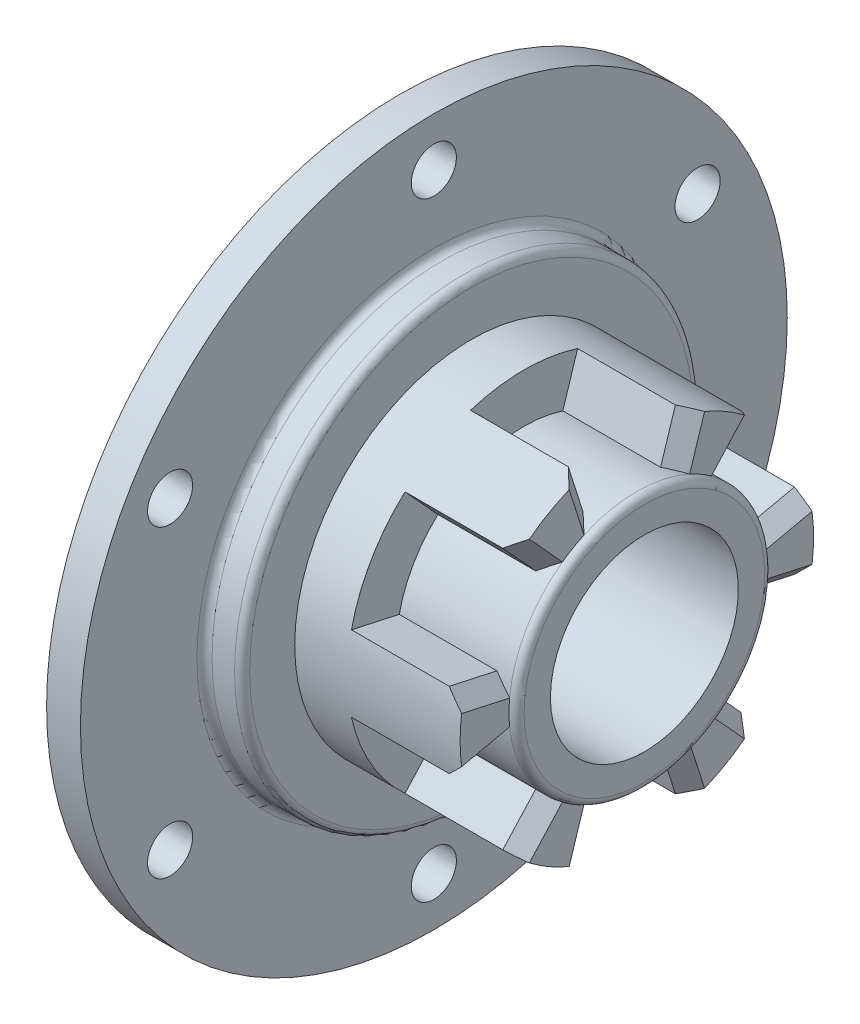
SolidWorks part; units mm, degrees
ref_plane "Front Plane" through (0, 0, 0) normal (0, 0, 1) x (1, 0, 0)
ref_plane "Top Plane" through (0, 0, 0) normal (0, 1, 0) x (1, 0, 0)
ref_plane "Right Plane" through (0, 0, 0) normal (1, 0, 0) x (0, 0, -1)
sketch "Sketch1" plane through (0, 0, 0) normal (0, 0, 1) x (1, 0, 0)
  line L0 (0, 31.5) -> (0, 34)
  line L1 (0, 34) -> (3.5, 34)
  line L2 (3.5, 34) -> (3.5, 47)
  line L3 (3.5, 47) -> (8, 47)
  line L4 (8, 47) -> (8, 30.5)
  line L5 (8, 30.5) -> (13, 30.5)
  line L6 (13, 30.5) -> (13, 23.5)
  line L7 (13, 23.5) -> (35, 23.5)
  line L8 (35, 23.5) -> (35, 17)
  line L9 (35, 17) -> (36, 17)
  line L10 (36, 17) -> (36, 12.5)
  line L11 (36, 12.5) -> (14, 12.5)
  line L12 (14, 12.5) -> (14, 14.5)
  line L13 (14, 14.5) -> (9.5, 14.5)
  line L14 (9.5, 14.5) -> (9.5, 27.0701)
  line L15 (9.5, 27.0701) -> (0, 31.5)
  line L16 (0, 0) -> (54.1966, 0) construction
  dimension "D1" = 4.5
  dimension "D2" = 47
  dimension "D3" = 34
  dimension "D4" = 2.5
  dimension "D5" = 115
  dimension "D6" = 5
  dimension "D7" = 4.5
  dimension "D8" = 6.5
  dimension "D9" = 7
  dimension "D10" = 12.5
  dimension "D11" = 3.5
  dimension "D12" = 2
  dimension "D13" = 4.5
  dimension "D14" = 22
  dimension "D15" = 1
  dimension "D16" = 22
revolve "Revolve1" add sketch "Sketch1" angle 360 about L16
sketch "Sketch2" plane through (35, 0, 0) normal (1, 0, 0) x (0, 0, -1)
  line L0 (0, 0) -> (0, 25.8657) construction
  line L1 (0, 0) -> (8.2062, 25.8067) construction
  line L2 (0, 0) -> (-8.2062, 25.8067) construction
  line L3 (-8.2062, 25.8067) -> (8.2062, 25.8067) construction
  line L4 (-7.1213, 22.395) -> (-5.1516, 16.2006)
  line L5 (7.1213, 22.395) -> (5.1516, 16.2006)
  arc A1 (5.1516, 16.2006) -> (-5.1516, 16.2006) centre (0, 0) ccw
  arc A2 (7.1213, 22.395) -> (-7.1213, 22.395) centre (0, 0) ccw
  dimension "D1" = 35.28
extrude "Cut-Extrude1" cut sketch "Sketch2" against normal blind 15
sketch "Sketch3" plane through (8, 0, 0) normal (1, 0, 0) x (0, 0, -1)
  circle A0 centre (0, 40.5) radius 3
  dimension "D1" = 6
  dimension "D2" = 40.5
extrude "Cut-Extrude2" cut sketch "Sketch3" against normal blind 15
pattern_circular "CirPattern2" count 6 over 360 about axis through (36, 0, 0) along (-1, 0, 0) of "Cut-Extrude2", "Cut-Extrude1"
fillet "Fillet1" radius 1 3 edges at (36, 0, 17) (8, 0, 30.5) (13, 0, 30.5)
chamfer "Chamfer1" distance 2 angle 45 12 edges at (35, 14.9632, -13.6442) (35, 19.2978, -6.1365) (35, 19.2978, 6.1365) (35, 14.9632, 13.6442) (35, -4.3346, 19.7806) (35, 4.3346, 19.7806) (35, -14.9632, 13.6442) (35, -19.2978, 6.1365) (35, -19.2978, -6.1365) (35, -14.9632, -13.6442) (35, -4.3346, -19.7806) (35, 4.3346, -19.7806)
scale "Scale1" scale about centroid uniform scaling yes scale factor 2
